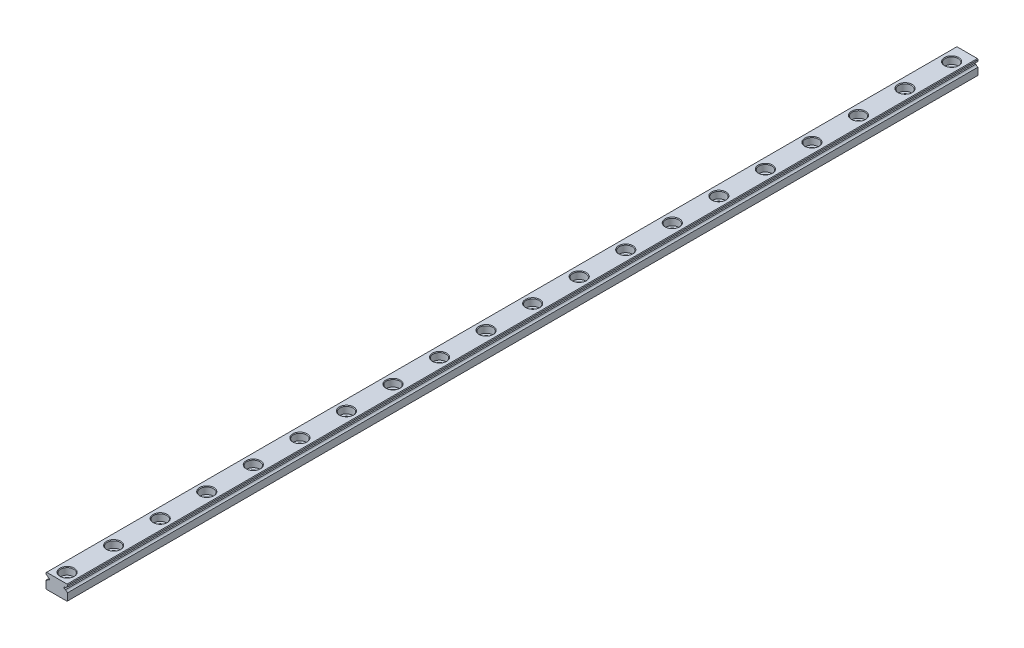
SolidWorks part; units mm, degrees
material "AISI 1020"
ref_plane "Спереди" through (0, 0, 0) normal (0, 0, 1) x (1, 0, 0)
ref_plane "Сверху" through (0, 0, 0) normal (0, 1, 0) x (1, 0, 0)
ref_plane "Справа" through (0, 0, 0) normal (1, 0, 0) x (0, 0, -1)
sketch "Sketch1" plane through (0, 0, 0) normal (0, 0, 1) x (1, 0, 0)
  line L0 (0, 0) -> (0, 4.3706) construction
  line L1 (-3.3, -2.4) -> (3.3, -2.4)
  line L2 (-3.5, -2.2) -> (-3.5, 0.1063)
  line L3 (-3.3, 2.4) -> (3.3, 2.4)
  line L4 (3.5, -2.2) -> (3.5, 0.1063)
  line L5 (-3.5, -2.4) -> (3.5, 2.4) construction
  line L6 (-3.5, 2.4) -> (3.5, -2.4) construction
  line L7 (-3.5, 1.6937) -> (-3.5, 2.2)
  line L8 (3.5, 1.6937) -> (3.5, 2.2)
  line L9 (-3.5, -2.2) -> (-3.3, -2.4)
  line L10 (3.3, -2.4) -> (3.5, -2.2)
  line L11 (3.3, 2.4) -> (3.5, 2.2)
  line L12 (-3.5, 2.2) -> (-3.3, 2.4)
  line L13 (2.8401, 0.65) -> (2.3401, 0.65)
  line L14 (-2.8401, 0.65) -> (-2.3401, 0.65)
  line L15 (2.3401, 0.65) -> (2.3401, 1.15)
  line L16 (-2.8401, 1.15) -> (-2.3401, 1.15)
  line L17 (-2.3401, 0.65) -> (-2.3401, 1.15)
  line L18 (2.8401, 1.15) -> (2.3401, 1.15)
  arc A0 (-3.5, 1.6937) -> (-2.8401, 1.15) centre (-3.6, 0.9) cw
  arc A1 (3.5, 1.6937) -> (2.8401, 1.15) centre (3.6, 0.9) ccw
  arc A2 (-2.8401, 0.65) -> (-3.5, 0.1063) centre (-3.6, 0.9) cw
  arc A3 (2.8401, 0.65) -> (3.5, 0.1063) centre (3.6, 0.9) ccw
  point P0 (0, 0)
  dimension "D4" = 0.8
  dimension "D5" = 0.1
  dimension "D1" = 7
  dimension "D2" = 4.8
  dimension "D3" = 1.5
  dimension "D6" = 0.5
  dimension "D7" = 0.5
extrude "Extrude1" add sketch "Sketch1" along normal offset from surface (293.3 mm away) 25
sketch "Sketch2" plane through (0, 2.4, 0) normal (0, 1, 0) x (1, 0, 0)
  line L0 (0, 0) -> (0, -5) construction
  circle A0 centre (0, -5) radius 1.2
  circle A1 centre (0, -5) radius 2.1
  dimension "D1" = 2.4
  dimension "D2" = 4.2
  dimension "D3" = 5
extrude "Extrude2" cut sketch "Sketch2" against normal up to next contours A0 region at (0, 2.4, 5)
extrude "Extrude4" cut sketch "Sketch" against normal blind 2.3
sketch "Sketch" plane through (0, 2.4, 0) normal (0, 1, 0) x (1, 0, 0) same geometry as "Sketch2"
chamfer "Chamfer1" distance 0.2 angle 45 2 edges at (0, -2.4, 6.2) (0, 2.4, 7.1)
pattern_linear "LPattern1" count 20 spacing 15 along (0, 0, 1) of "Extrude4", "Chamfer1", "Extrude2"
